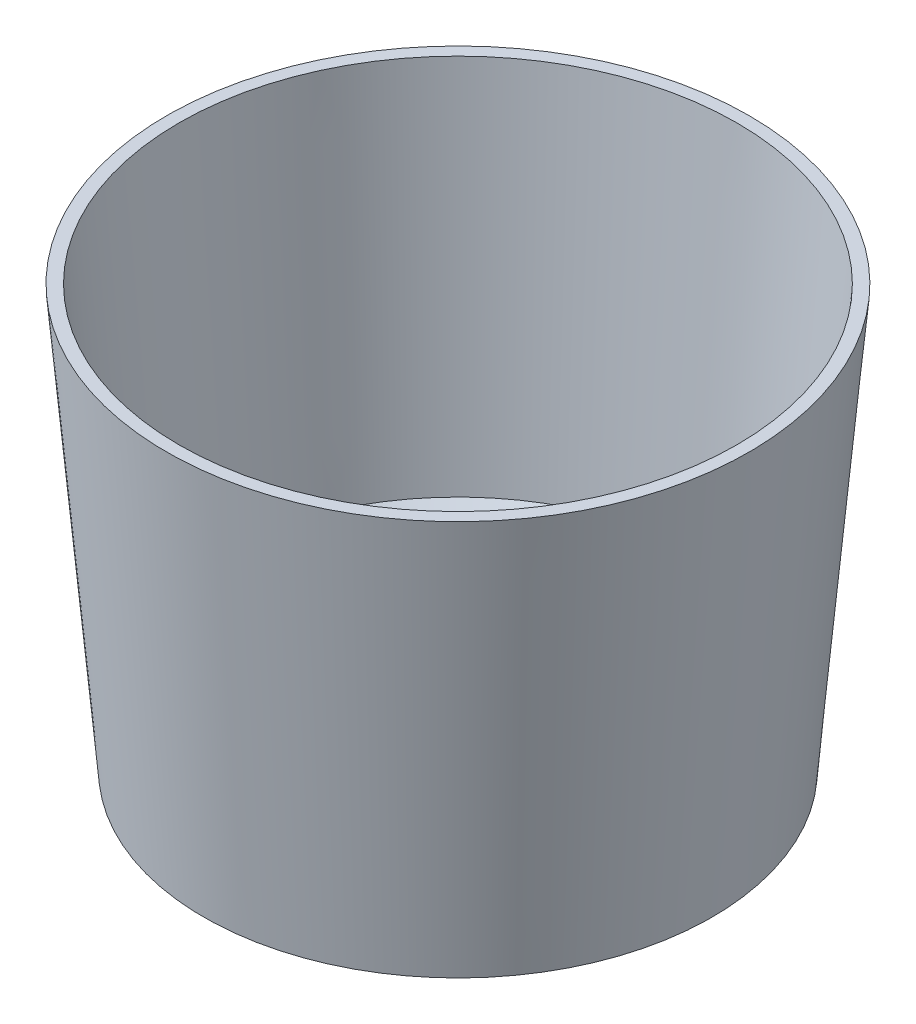
SolidWorks part; units mm, degrees
note: '?' marks a value the reader was unsure of. The reader was unsure of these and kept them because the rebuilt part matched: shared geometry of "Schizzo10<7>", "Schizzo13<3>".
ref_plane "Piano frontale" through (0, 0, 0) normal (0, 0, 1) x (1, 0, 0)
ref_plane "Piano superiore" through (0, 0, 0) normal (0, 1, 0) x (1, 0, 0)
ref_plane "Piano destro" through (0, 0, 0) normal (1, 0, 0) x (0, 0, -1)
sketch "Schizzo1" plane through (0, 0, 0) normal (0, 1, 0) x (1, 0, 0)
  circle A0 centre (0, 0) radius 61.5
  dimension "D1" = 123
ref_plane "Piano1" through (0, 102, 0) normal (0, 1, 0) x (1, 0, 0)
sketch "Schizzo2" plane through (0, 102, 0) normal (0, 1, 0) x (1, 0, 0)
  circle A0 centre (0, 0) radius 67.5
  dimension "D1" = 135
sketch "Schizzo5" plane through (0, 102, 0) normal (0, 1, 0) x (1, 0, 0)
  circle A0 centre (0, 0) radius 70.5
  circle A1 centre (0, 0) radius 67.5 construction
  dimension "D1" = 3
sketch "Schizzo4" plane through (0, 0, 0) normal (0, 0, 1) x (1, 0, 0)
  line L0 (-70.5, 102) -> (-61.5, 0)
  line L2 (61.5, 0) -> (-61.5, 0) construction
  line L3 (-61.5, 0) -> (0, 0)
  line L4 (0, 0) -> (0, 102)
  line L5 (67.5, 102) -> (-67.5, 102) construction
  line L6 (0, 102) -> (-70.5, 102)
  point P2 (0, 0)
  point P3 (0, 0)
  point P6 (0, 0)
  point P11 (0, 0)
revolve "Rivoluzione1" add sketch "Schizzo4" angle 360 about L4
ref_plane "Piano2" through (0, 12, 0) normal (0, 1, 0) x (1, 0, 0)
sketch "Schizzo8" plane through (0, 12, 0) normal (0, 1, 0) x (1, 0, 0)
  circle A0 centre (0, 0) radius 60
  point P3 (0, 0)
  point P4 (0, -6.8284)
  point P5 (0, 0)
  point P6 (0, 0)
  point P8 (0, 0)
  dimension "D1" = 120
sketch "Schizzo7" plane through (0, 0, 0) normal (0, 0, 1) x (1, 0, 0)
  line L0 (0, 102) -> (-67.5, 102)
  line L1 (67.5, 102) -> (-67.5, 102) construction
  line L2 (-67.5, 102) -> (-60, 12)
  line L3 (79.75, 12) -> (-79.75, 12) construction
  line L4 (-60, 12) -> (0, 12)
  line L5 (0, 12) -> (0, 102)
  point P7 (0, 0)
  point P9 (0, 0)
  point P13 (0, 0)
ref_axis "Assi1" through (0, 102, 0) along (0, -1, 0)?
revolve "Taglia-Rivoluzione1" cut sketch "Schizzo7" angle 360 about L5
sketch "Schizzo9" plane through (0, 0, 0) normal (0, -1, 0) x (1, 0, 0)
  circle A0 centre (0, 0) radius 56.5
  circle A1 centre (0, 0) radius 61.5 construction
  dimension "D1" = 5
extrude "Taglio-Estrusione1" cut sketch "Schizzo9" against normal blind 7.5 contours A0
sketch "Schizzo10" plane through (0, 0, 0) normal (0, -1, 0) x (1, 0, 0)
  line L0 (0, 0) -> (0, 103.2061) construction
  line L1 (0, 59) -> (0, 56.5)
  line L3 (20, 52.8417) -> (20, 55.5068)
  line L4 (0, 59) -> (0, 56.5)
  line L5 (5, 58.7878) -> (5, 56.2783)
  line L6 (10, 58.1464) -> (10, 55.608)
  circle A0 centre (0, 0) radius 59 construction
  circle A1 centre (0, 0) radius 56.5 construction
  arc A3 (0, 56.5) -> (20, 52.8417) centre (0, 0) cw
  circle A4 centre (0, 0) radius 56.5 construction
  arc A7 (0, 59) -> (20, 55.5068) centre (0, 0) cw
  circle A9 centre (12.5, 55.0999) radius 0.6
  point P11 (0, 0)
  point P20 (0, 0)
  point P21 (0, 0)
  dimension "D1" = 2.5
  dimension "D5" = 10
  dimension "D6" = 1.2
  dimension "D2" = 2.5
  dimension "D3" = 5
  dimension "D4" = 5
extrude "Taglio-Estrusione2" cut sketch "Schizzo10" against normal blind 5
extrude "Estrusione-Estrusione1" add sketch "Schizzo10<7>" against normal blind 2.4
sketch "Schizzo10<7>" plane through (0, 0, 0) normal (0, -1, 0) x (1, 0, 0) same geometry as "Schizzo10"
chamfer "Smusso1" distance 1.25 3 edges at (16.5762, 2.4, 54.0137) (15.058, 2.4, 57.0461) (10.9587, 2.4, 55.427)
chamfer "Smusso2" distance 2.5 angle 45 1 edges at (10.1659, 5, 55.5779)
pattern_circular "RipetizioneCircolare3" count 3 every 120 about axis through (0, 0, 0) along (0, 1, 0) of "Taglio-Estrusione2", "Estrusione-Estrusione1", "Smusso1", "Smusso2"
chamfer "Smusso4" distance 2.5 angle 45 3 edges at (-43.0489, 7.5, 36.5929) (-10.1659, 7.5, -55.5779) (53.2148, 7.5, 18.985)
chamfer "Smusso5" distance 2.5 angle 45 1 edges at (0, 12, -60)
sketch "Schizzo13" plane through (0, 12, 0) normal (0, 1, 0) x (1, 0, 0)
  line L0 (-52.2133, 21.0947) -> (-42.0053, 37.1196)
  line L1 (-32.9588, 28.9857) -> (-41.393, 34.3583)
  line L2 (-32.9588, 28.9857) -> (-41.0178, 16.3344)
  line L3 (-41.0178, 16.3344) -> (-49.4519, 21.7071)
  line L4 (-41.393, 34.3583) -> (-49.4519, 21.7071)
  line L5 (-52.2133, 21.0947) -> (-40.4055, 13.5731)
  line L6 (-42.0053, 37.1196) -> (-30.1975, 29.598)
  line L7 (-40.4055, 13.5731) -> (-30.1975, 29.598)
  point P4 (0, 0)
  point P7 (0, 0)
  point P10 (0, 0)
  point P11 (0, 0)
  point P12 (-30.1975, 28.9857)
  dimension "D1" = 15
  dimension "D2" = 10
  dimension "D3" = 2
  dimension "D4" = 2
  dimension "D5" = 2
  dimension "D6" = 2
  dimension "D7" = 8.7394
extrude "Taglio-Estrusione3" cut sketch "Schizzo13" against normal up to next contours L1 L4 L3 L2
extrude "Estrusione-Estrusione2" add sketch "Schizzo13<3>" along normal blind 1 contours L5 L7 L6 L0 L4 L1 L2 L3
sketch "Schizzo13<3>" plane through (0, 12, 0) normal (0, 1, 0) x (1, 0, 0) same geometry as "Schizzo13"
chamfer "Smusso7" distance 2 angle 30 4 edges at (-46.3094, 12, -17.3339) (-35.3015, 12, -21.5855) (-36.1014, 12, -33.3588) (-47.1093, 12, -29.1072)
